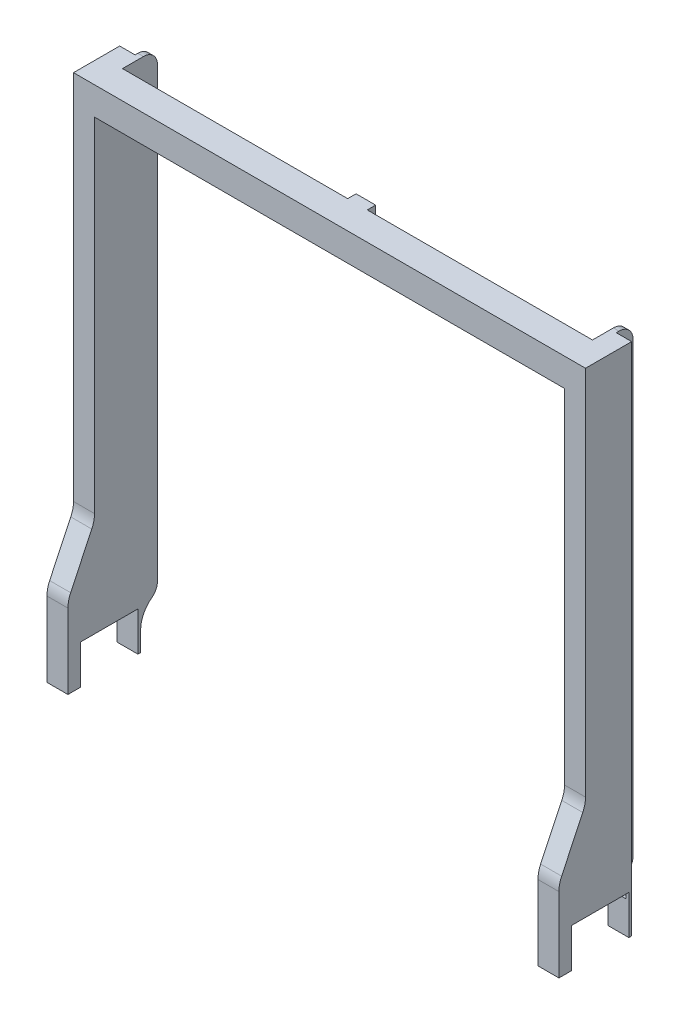
SolidWorks part; units mm, degrees
ref_plane "정면" through (0, 0, 0) normal (0, 0, 1) x (1, 0, 0)
ref_plane "윗면" through (0, 0, 0) normal (0, 1, 0) x (1, 0, 0)
ref_plane "우측면" through (0, 0, 0) normal (1, 0, 0) x (0, 0, -1)
sketch "스케치1" plane through (0, 0, 0) normal (0, 0, 1) x (1, 0, 0)
  line L0 (-318.5049, 0) -> (318.5049, 0) construction
  line L1 (0, 0) -> (0, -258.8265) construction
  line L2 (-168, 0) -> (168, 0)
  line L3 (-168, -20) -> (168, -20)
  line L4 (168, -20) -> (168, 0) construction
  line L5 (168, -20) -> (168, -340)
  line L6 (172, -340) -> (172, 0)
  line L7 (168, 0) -> (183, 0)
  line L8 (183, 0) -> (183, -340)
  line L9 (183, -340) -> (168, -340)
  line L10 (-168, -20) -> (-168, 0) construction
  line L11 (-183, -340) -> (-168, -340)
  line L12 (-183, 0) -> (-183, -340)
  line L13 (-168, 0) -> (-183, 0)
  line L14 (-172, -340) -> (-172, 0)
  line L15 (-168, -20) -> (-168, -340)
  line L16 (168, -20) -> (168, 0)
  line L17 (-168, -20) -> (-168, 0)
  point P14 (0, -20)
  dimension "D1" = 168
  dimension "D2" = 20
  dimension "D3" = 4
  dimension "D4" = 340
  dimension "D5" = 15
extrude "보스-돌출1" add sketch "스케치1" along normal blind 26 contours L3 L5 L9 L8 L7 L2 L13 L12 L11 L15
extrude "보스-돌출2" add sketch "스케치1<4>" against normal blind 19 contours L16 L5 L9 L6 L7 | L15 L17 L13 L14 L11 region at (-170, -170, 0) region at (170, -170, 0)
sketch "스케치1<4>" plane through (0, 0, 0) normal (0, 0, 1) x (1, 0, 0) same geometry as "스케치1"
fillet "필렛1" radius 10 4 edges at (-170, 0, -19) (170, 0, -19) (170, -340, -19) (-170, -340, -19)
sketch "스케치2" plane through (172, 0, 0) normal (1, 0, 0) x (0, 0, -1)
  line L0 (14, -340) -> (14, 0)
  line L1 (12, 0) -> (12, -340)
  line L4 (19, -330) -> (19, -10)
  line L5 (9, 0) -> (0, 0)
  line L6 (0, 0) -> (0, -340)
  line L7 (0, -340) -> (9, -340)
  line L8 (19, -330) -> (19, -10)
  line L9 (9, 0) -> (0, 0)
  line L10 (0, 0) -> (0, -340)
  line L11 (0, -340) -> (9, -340)
  arc A2 (19, -10) -> (9, 0) centre (9, -10) ccw
  arc A3 (9, -340) -> (19, -330) centre (9, -330) ccw
  arc A4 (19, -10) -> (9, 0) centre (9, -10) ccw
  arc A5 (9, -340) -> (19, -330) centre (9, -330) ccw
  dimension "D2" = 5
  dimension "D3" = 2
  dimension "D1" = 0
sketch "스케치3" plane through (168, 0, 0) normal (-1, 0, 0) x (0, 0, 1)
  line L0 (-12, 0) -> (-12, -340) construction
  line L1 (-14, -340) -> (-14, 0) construction
  line L2 (-12, 0) -> (-12, -340)
  line L3 (-14, -340) -> (-14, 0)
  line L4 (-19, -10) -> (-19, -330)
  line L5 (0, 0) -> (-9, 0)
  line L6 (0, -340) -> (0, 0)
  line L7 (-9, -340) -> (0, -340)
  line L8 (-19, -10) -> (-19, -330)
  line L9 (0, 0) -> (-9, 0)
  line L10 (0, -340) -> (0, 0)
  line L11 (-9, -340) -> (0, -340)
  arc A2 (-9, 0) -> (-19, -10) centre (-9, -10) ccw
  arc A3 (-19, -330) -> (-9, -340) centre (-9, -330) ccw
  arc A4 (-9, 0) -> (-19, -10) centre (-9, -10) ccw
  arc A5 (-19, -330) -> (-9, -340) centre (-9, -330) ccw
  dimension "D1" = 0
sketch "스케치5" plane through (0, 0, 0) normal (0, 1, 0) x (1, 0, 0)
  line L0 (-7, 0) -> (-7, -26)
  line L1 (7, 0) -> (7, -26)
  line L2 (-168, 0) -> (-168, -6)
  line L3 (-168, -6) -> (-7, -6)
  line L4 (7, -6) -> (168, -6)
  line L5 (168, -6) -> (168, 0)
  line L12 (-168, 0) -> (-168, 9)
  line L13 (-168, 9) -> (-172, 9)
  line L14 (-172, 9) -> (-172, 0)
  line L15 (-172, 0) -> (-183, 0)
  line L16 (-183, 0) -> (-183, -26)
  line L17 (-183, -26) -> (183, -26)
  line L18 (183, -26) -> (183, 0)
  line L19 (183, 0) -> (172, 0)
  line L20 (172, 0) -> (172, 9)
  line L21 (172, 9) -> (168, 9)
  line L22 (168, 9) -> (168, 0)
  line L23 (168, 0) -> (-168, 0)
  line L24 (-168, 0) -> (-168, 9)
  line L25 (-168, 9) -> (-172, 9)
  line L26 (-172, 9) -> (-172, 0)
  line L27 (-172, 0) -> (-183, 0)
  line L28 (-183, 0) -> (-183, -26)
  line L29 (-183, -26) -> (183, -26)
  line L30 (183, -26) -> (183, 0)
  line L31 (183, 0) -> (172, 0)
  line L32 (172, 0) -> (172, 9)
  line L33 (172, 9) -> (168, 9)
  line L34 (168, 9) -> (168, 0)
  line L35 (168, 0) -> (-168, 0)
  line M27 (168, 0) -> (-168, 0)
  dimension "D2" = 7
  dimension "D3" = 7
  dimension "D4" = 6
  dimension "D1" = 0
extrude "컷-돌출1" cut sketch "스케치5" against normal blind 52 contours L2 L3 L0 M27 | L4 L5 L1 M27 region at (-87.5, 0, 3) region at (87.5, 0, 3)
extrude "보스-돌출4" add sketch "스케치1<5>" against normal blind 7 contours L9 L8 L7 L6 | L11 L14 L13 L12 region at (-177.5, -170, 0) region at (177.5, -170, 0)
sketch "스케치1<5>" plane through (0, 0, 0) normal (0, 0, 1) x (1, 0, 0) same geometry as "스케치1"
sketch "스케치6" plane through (0, -340, 0) normal (0, -1, 0) x (1, 0, 0)
  line L0 (-172, -7) -> (-126.7636, -7) construction
  line L1 (-172, -7) -> (-168, -7)
  line L2 (-168, -7) -> (-168, -5)
  line L3 (-168, -5) -> (-174.5, -5)
  line L4 (-174.5, -5) -> (-174.5, -7)
  line L5 (-181.1, -7) -> (-181.1, -5)
  line L6 (-172, -7) -> (-172, -9)
  line L7 (-172, -9) -> (-168, -9)
  line L8 (-168, -9) -> (-168, 26)
  line L9 (-168, 26) -> (-183, 26)
  line L10 (-183, 26) -> (-183, -7)
  line L11 (-183, -7) -> (-172, -7)
  line L12 (-172, -7) -> (-172, -9)
  line L13 (-172, -9) -> (-168, -9)
  line L14 (-168, -9) -> (-168, 26)
  line L15 (-168, 26) -> (-183, 26)
  line L16 (-183, 26) -> (-183, -7)
  line L17 (-183, -7) -> (-172, -7)
  line L18 (-181.1, -5) -> (-183, -5)
  line L19 (-181.1, -5) -> (-174.5, -5)
  line L20 (-168, 26) -> (-168, 36)
  line L21 (-168, 36) -> (-183, 36)
  line L22 (-183, 36) -> (-183, 26)
  line L23 (-168, 36) -> (-168, 45)
  line L24 (-168, 45) -> (-183, 45)
  line L25 (-183, 45) -> (-183, 36)
  line M14 (-168, -9) -> (-168, 26)
  line M15 (-168, 26) -> (-183, 26)
  line M17 (-183, -7) -> (-172, -7)
  dimension "D2" = 6.5
  dimension "D3" = 2
  dimension "D4" = 6.6
  dimension "D5" = 41
  dimension "D6" = 9
  dimension "D1" = 0
extrude "보스-돌출5" add sketch "스케치6" along normal blind 28 contours L5 L18 L16 M17 | L19 L5 L4 M17 | L3 L4 L1 M17 M14 region at (-171.25, -340, -6) region at (-177.8, -340, -6) region at (-182.05, -340, -6)
extrude "컷-돌출2" cut sketch "스케치6<3>" along normal blind 5 contours L19 L5 L4 M17 region at (-177.8, -340, -6)
sketch "스케치6<3>" plane through (0, -340, 0) normal (0, -1, 0) x (1, 0, 0) same geometry as "스케치6"
fillet "필렛2" radius 20 1 edges at (-170, -340, -7)
extrude "보스-돌출6" add sketch "스케치6<4>" against normal blind 30 contours L21 L22 L20 M15 | L24 L25 L21 L23 region at (-175.5, -340, 31) region at (-175.5, -340, 40.5)
sketch "스케치6<4>" plane through (0, -340, 0) normal (0, -1, 0) x (1, 0, 0) same geometry as "스케치6"
extrude "보스-돌출7" add sketch "스케치6<5>" along normal blind 28 contours L24 L25 L21 L23 region at (-175.5, -340, 40.5)
sketch "스케치6<5>" plane through (0, -340, 0) normal (0, -1, 0) x (1, 0, 0) same geometry as "스케치6"
sketch "스케치9" plane through (-183, 0, 0) normal (-1, 0, 0) x (0, 0, 1)
  line L0 (45, -310) -> (26, -270)
  line L1 (26, 0) -> (26, -310) construction
  line L12 (26, 0) -> (-7, 0)
  line L13 (-7, 0) -> (-7, -368)
  line L14 (-7, -368) -> (-5, -368)
  line L15 (-5, -368) -> (-5, -340)
  line L16 (-5, -340) -> (36, -340)
  line L17 (36, -340) -> (36, -368)
  line L18 (36, -368) -> (45, -368)
  line L19 (45, -368) -> (45, -310)
  line L20 (45, -310) -> (26, -310)
  line L21 (26, -310) -> (26, 0)
  line L22 (26, 0) -> (-7, 0)
  line L23 (-7, 0) -> (-7, -368)
  line L24 (-7, -368) -> (-5, -368)
  line L25 (-5, -368) -> (-5, -340)
  line L26 (-5, -340) -> (36, -340)
  line L27 (36, -340) -> (36, -368)
  line L28 (36, -368) -> (45, -368)
  line L29 (45, -368) -> (45, -310)
  line L30 (45, -310) -> (26, -310)
  line L31 (26, -310) -> (26, 0)
  line M19 (45, -310) -> (26, -310)
  line M20 (26, -310) -> (26, 0)
  dimension "D2" = 40
  dimension "D1" = 0
extrude "보스-돌출8" add sketch "스케치9" against normal blind 15 contours L0 M19 M20 region at (-183, -296.6667, 32.3333)
fillet "필렛3" radius 20 2 edges at (-175.5, -270, 26) (-175.5, -310, 45)
mirror "대칭 복사2" about plane through (0, 0, 0) normal (1, 0, 0) of "보스-돌출5", "컷-돌출2", "필렛3", "보스-돌출6", "보스-돌출7", "보스-돌출8"
fillet "필렛4" radius 20 1 edges at (170, -340, -7)
sketch "스케치10" plane through (183, 0, 0) normal (1, 0, 0) x (0, 0, -1)
  line L0 (-27.9344, -274.0725) -> (-43.0656, -305.9275) construction
  line L1 (-45, -314.5086) -> (-45, -368) construction
  line L2 (-45, -368) -> (-36, -368) construction
  line L3 (-36, -368) -> (-36, -340) construction
  line L4 (-36, -340) -> (5, -340) construction
  line L5 (5, -340) -> (5, -368) construction
  line L6 (5, -368) -> (7, -368) construction
  line L7 (7, -368) -> (7, -354) construction
  line L8 (19, -330) -> (19, -10) construction
  line L9 (9, 0) -> (-6, 0) construction
  line L10 (-6, 0) -> (-6, -20) construction
  line L11 (-6, -20) -> (-26, -20) construction
  line L12 (-26, -20) -> (-26, -265.4914) construction
  line L13 (-27.9344, -274.0725) -> (-43.0656, -305.9275) construction
  line L14 (-45, -314.5086) -> (-45, -368) construction
  line L15 (-45, -368) -> (-36, -368) construction
  line L16 (-36, -368) -> (-36, -340) construction
  line L17 (-36, -340) -> (5, -340) construction
  line L18 (5, -340) -> (5, -368) construction
  line L19 (5, -368) -> (7, -368) construction
  line L20 (7, -368) -> (7, 0) construction
  line L21 (7, 0) -> (-26, 0) construction
  line L22 (-26, 0) -> (-26, -265.4914) construction
  line L23 (-27.9344, -274.0725) -> (-43.0656, -305.9275)
  line L24 (-45, -314.5086) -> (-45, -368)
  line L25 (-45, -368) -> (-36, -368)
  line L26 (-36, -368) -> (-36, -340)
  line L27 (-36, -340) -> (5, -340)
  line L28 (5, -340) -> (5, -368)
  line L29 (5, -368) -> (7, -368)
  line L30 (7, -368) -> (7, -354)
  line L31 (19, -330) -> (19, -10)
  line L32 (9, 0) -> (-6, 0)
  line L33 (-6, 0) -> (-6, -20)
  line L34 (-6, -20) -> (-26, -20)
  line L35 (-26, -20) -> (-26, -265.4914)
  line L36 (-27.9344, -274.0725) -> (-43.0656, -305.9275)
  line L37 (-45, -314.5086) -> (-45, -368)
  line L38 (-45, -368) -> (-36, -368)
  line L39 (-36, -368) -> (-36, -340)
  line L40 (-36, -340) -> (5, -340)
  line L41 (5, -340) -> (5, -368)
  line L42 (5, -368) -> (7, -368)
  line L43 (7, -368) -> (7, 0)
  line L44 (7, 0) -> (-26, 0)
  line L45 (-26, 0) -> (-26, -265.4914)
  line L46 (-26, -10) -> (-6, -10)
  arc A0 (-43.0656, -305.9275) -> (-45, -314.5086) centre (-25, -314.5086) ccw construction
  arc A1 (15, -338) -> (7, -354) centre (27, -354) ccw construction
  arc A2 (15, -338) -> (19, -330) centre (9, -330) ccw construction
  arc A3 (19, -10) -> (9, 0) centre (9, -10) ccw construction
  arc A4 (-27.9344, -274.0725) -> (-26, -265.4914) centre (-46, -265.4914) ccw construction
  arc A5 (-43.0656, -305.9275) -> (-45, -314.5086) centre (-25, -314.5086) ccw construction
  arc A6 (-27.9344, -274.0725) -> (-26, -265.4914) centre (-46, -265.4914) ccw construction
  arc A7 (-43.0656, -305.9275) -> (-45, -314.5086) centre (-25, -314.5086) ccw
  arc A8 (15, -338) -> (7, -354) centre (27, -354) ccw
  arc A9 (15, -338) -> (19, -330) centre (9, -330) ccw
  arc A10 (19, -10) -> (9, 0) centre (9, -10) ccw
  arc A11 (-27.9344, -274.0725) -> (-26, -265.4914) centre (-46, -265.4914) ccw
  arc A12 (-43.0656, -305.9275) -> (-45, -314.5086) centre (-25, -314.5086) ccw
  arc A13 (-27.9344, -274.0725) -> (-26, -265.4914) centre (-46, -265.4914) ccw
